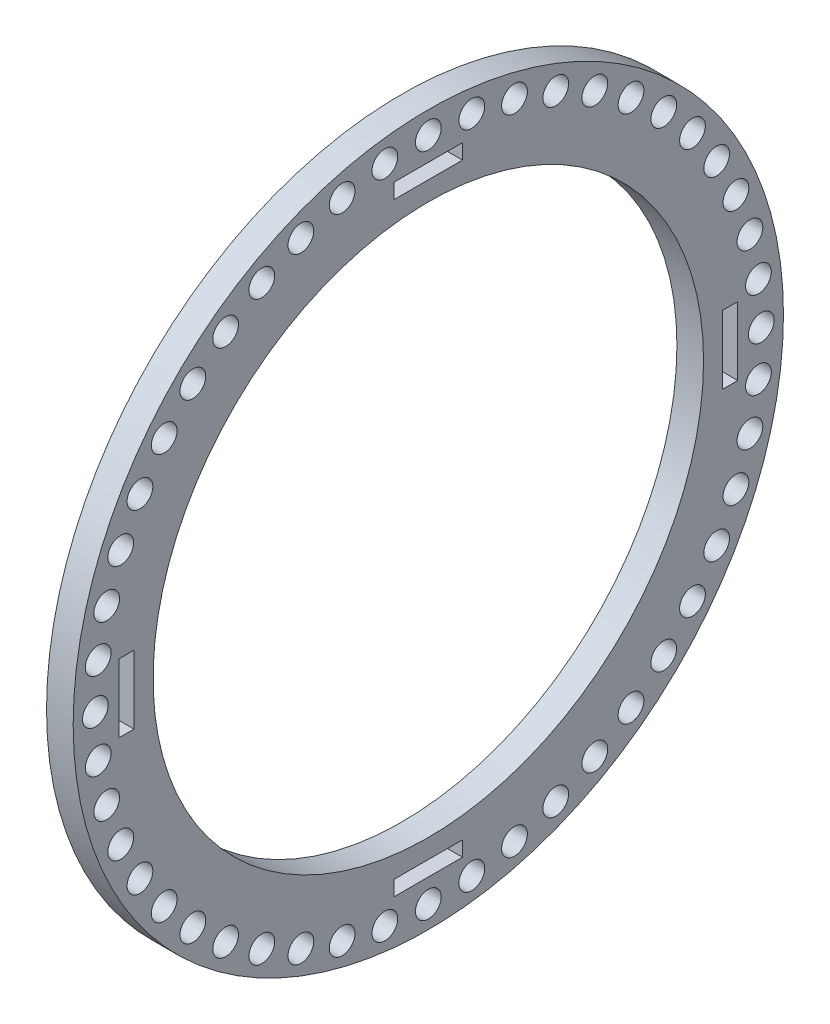
SolidWorks part; units mm, degrees
material "AISI 304"
ref_plane "Front Plane" through (0, 0, 0) normal (0, 0, 1) x (1, 0, 0)
ref_plane "Top Plane" through (0, 0, 0) normal (0, 1, 0) x (1, 0, 0)
ref_plane "Right Plane" through (0, 0, 0) normal (1, 0, 0) x (0, 0, -1)
sketch "Sketch1" plane through (0, 0, 0) normal (1, 0, 0) x (0, 0, -1)
  line L0 (0, 0) -> (0, 40) construction
  line L62 (-3.85, 34.85) -> (3.85, 34.85)
  line L63 (-3.85, 34.85) -> (-3.85, 33.15)
  line L64 (-3.85, 33.15) -> (3.85, 33.15)
  line L65 (3.85, 34.85) -> (3.85, 33.15)
  line L66 (-3.85, 34.85) -> (3.85, 33.15) construction
  line L67 (-3.85, 33.15) -> (3.85, 34.85) construction
  line L103 (34.85, 3.85) -> (34.85, -3.85)
  line L104 (33.15, 3.85) -> (33.15, -3.85)
  line L105 (34.85, 3.85) -> (33.15, 3.85)
  line L106 (34.85, -3.85) -> (33.15, -3.85)
  line L107 (3.85, -34.85) -> (-3.85, -34.85)
  line L108 (3.85, -33.15) -> (-3.85, -33.15)
  line L109 (3.85, -34.85) -> (3.85, -33.15)
  line L110 (-3.85, -34.85) -> (-3.85, -33.15)
  line L111 (-34.85, -3.85) -> (-34.85, 3.85)
  line L112 (-33.15, -3.85) -> (-33.15, 3.85)
  line L113 (-34.85, -3.85) -> (-33.15, -3.85)
  line L114 (-34.85, 3.85) -> (-33.15, 3.85)
  circle A3 centre (0, 0) radius 40
  circle A25 centre (0, 0) radius 31
  point P9 (0, -20)
  point P11 (-20, 0)
  point P22 (0, 34)
  point P29 (20, 0)
  point P31 (0, 30)
  point P75 (0, 0)
  point P81 (0, -1)
  point P93 (0, 0)
  point P95 (0, 0)
  dimension "D2" = 80
  dimension "D3" = 62
  dimension "D7" = 7.7
  dimension "D8" = 1.7
  dimension "D9" = 10
  dimension "D12" = 6
  dimension "D14" = 4
extrude "Boss-Extrude4" add sketch "Sketch1" along normal blind 3
sketch "Sketch2" plane through (3, 0, 0) normal (1, 0, 0) x (0, 0, -1)
  circle A0 centre (0, 37.5) radius 1.45
  circle A1 centre (0, 0) radius 40 construction
  dimension "D2" = 2.9
  dimension "D1" = 37.5
extrude "Cut-Extrude2" cut sketch "Sketch2" against normal up to next
pattern_circular "CirPattern3" count 48 over 360 about axis through (3, 0, 0) along (1, 0, 0) of "Cut-Extrude2"
